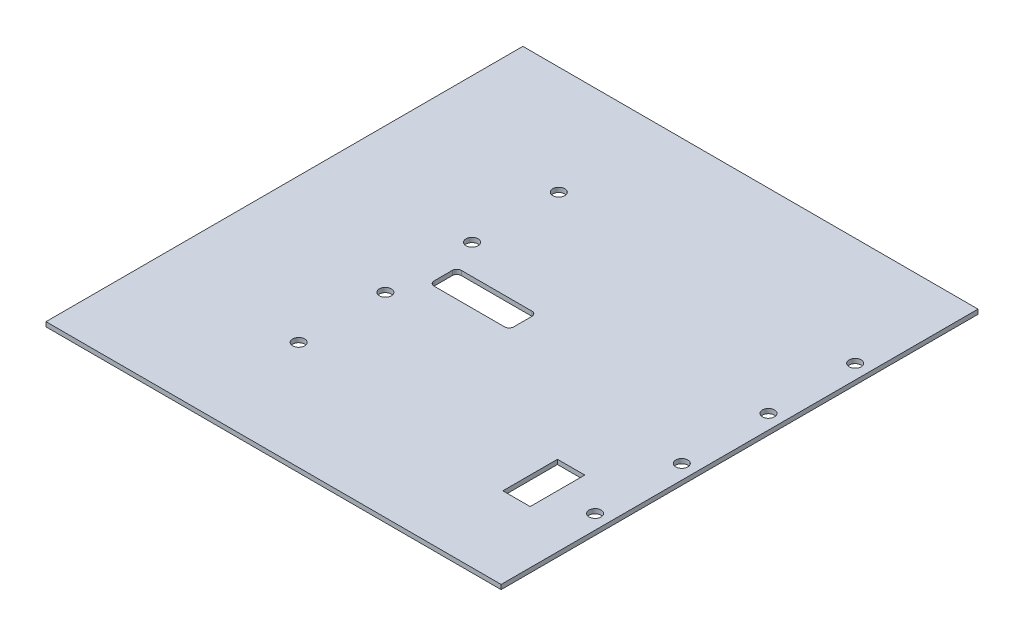
SolidWorks part; units mm, degrees
material "Thornel Mat VMA"
ref_plane "Front Plane" through (0, 0, 0) normal (0, 0, 1) x (1, 0, 0)
ref_plane "Top Plane" through (0, 0, 0) normal (0, 1, 0) x (1, 0, 0)
ref_plane "Right Plane" through (0, 0, 0) normal (1, 0, 0) x (0, 0, -1)
sketch "Sketch1" plane through (0, 0, 0) normal (0, 1, 0) x (1, 0, 0)
  line L1 (-100, -104.775) -> (100, -104.775)
  line L2 (-100, -104.775) -> (-100, 104.775)
  line L3 (-100, 104.775) -> (100, 104.775)
  line L4 (100, -104.775) -> (100, 104.775)
  line L5 (-100, -104.775) -> (100, 104.775) construction
  line L6 (-100, 104.775) -> (100, -104.775) construction
  point P0 (0, 0)
  dimension "D1" = 200
  dimension "D2" = 209.55
extrude "Boss-Extrude1" add sketch "Sketch1" along normal mid plane 2
sketch "Sketch2" plane through (0, 1, 0) normal (0, 1, 0) x (1, 0, 0)
  line L0 (-100, -104.775) -> (100, -104.775) construction
  line L1 (100, 104.775) -> (87.3, 104.775) construction
  line L2 (100, 104.775) -> (100, -104.775) construction
  line L3 (100, -104.775) -> (87.3, -104.775) construction
  line L4 (87.3, 104.775) -> (87.3, -104.775) construction
  line L5 (100, 104.775) -> (-100, 104.775) construction
  line L6 (-30.25, 104.775) -> (-42.95, 104.775) construction
  line L7 (-30.25, 104.775) -> (-30.25, -104.775) construction
  line L8 (-30.25, -104.775) -> (-42.95, -104.775) construction
  line L9 (-42.95, 104.775) -> (-42.95, -104.775) construction
  line L10 (93.65, 104.775) -> (93.65, -104.775) construction
  line L11 (-36.6, 104.775) -> (-36.6, -104.775) construction
  point P17 (93.65, 57.15)
  point P18 (-36.6, 57.15)
  point P20 (93.65, 19.05)
  point P21 (-36.6, 19.05)
  point P22 (93.65, -19.05)
  point P23 (-36.6, -19.05)
  point P24 (93.65, -57.15)
  point P25 (-36.6, -57.15)
  dimension "D1" = 12.7
  dimension "D2" = 12.7
  dimension "D3" = 130.25
  dimension "D4" = 47.625
  dimension "D6" = 38.1
  dimension "D5" = 4
hole_wizard "M5 Clearance Hole1" positions "Sketch3" profile "Sketch4" hole size "M5" standard "ANSI Metric" end condition up to next
sketch "Sketch3" plane through (0, 1, 0) normal (0, 1, 0) x (1, 0, 0)
  point P0 (-36.6, 57.15)
  point P3 (-36.6, 19.05)
  point P6 (-36.6, -19.05)
  point P9 (-36.6, -57.15)
  point P12 (93.65, -57.15)
  point P15 (93.65, -19.05)
  point P18 (93.65, 19.05)
  point P21 (93.65, 57.15)
sketch "Sketch4" plane through (-36.6, 1, -57.15) normal (1, 0, 0) x (0, 0, 1)
  line L0 (0, 0) -> (0, 2)
  line L1 (0, 2) -> (2.65, 2)
  line L2 (2.65, 2) -> (2.65, 0)
  line L5 (2.65, 0) -> (0, 0)
  line L11 (0, -6.35) -> (0, 107.95) construction
  dimension "Thru Hole Dia." = 5.3
  dimension "Thru Hole Depth" = 2
sketch "Sketch5" plane through (0, 1, 0) normal (0, 1, 0) x (1, 0, 0)
  line L0 (-30.25, 104.775) -> (-30.25, -104.775) construction
  line L1 (100, 104.775) -> (-100, 104.775) construction
  line L2 (-100, -104.775) -> (100, -104.775) construction
  line L3 (0, 0) -> (100, 0) construction
  line L4 (4.75, -6) -> (-30.25, -6)
  line L5 (4.75, -6) -> (4.75, 6)
  line L6 (4.75, 6) -> (-30.25, 6)
  line L7 (-30.25, -6) -> (-30.25, 6)
  line L8 (4.75, -6) -> (-30.25, 6) construction
  line L9 (4.75, 6) -> (-30.25, -6) construction
  line L10 (100, -104.775) -> (100, 104.775) construction
  circle A2 centre (-36.6, 19.05) radius 2.65 construction
  point P12 (-12.75, 0)
  dimension "D4" = 6.35
  dimension "D5" = 12
  dimension "D6" = 35
extrude "Cut-Extrude1" cut sketch "Sketch5" against normal through all
fillet "Fillet1" radius 2 4 edges at (4.75, 0, 6) (-30.25, 0, 6) (4.75, 0, -6) (-30.25, 0, -6)
sketch "Sketch8" plane through (0, 1, 0) normal (0, 1, 0) x (1, 0, 0)
  line L0 (100, -104.775) -> (100, 104.775) construction
  line L1 (64.75, -68.775) -> (76.75, -68.775)
  line L2 (64.75, -68.775) -> (64.75, -44.775)
  line L3 (64.75, -44.775) -> (76.75, -44.775)
  line L4 (76.75, -68.775) -> (76.75, -44.775)
  line L5 (64.75, -68.775) -> (76.75, -44.775) construction
  line L6 (64.75, -44.775) -> (76.75, -68.775) construction
  line L7 (-100, -104.775) -> (100, -104.775) construction
  point P0 (70.75, -56.775)
  dimension "D1" = 12
  dimension "D2" = 24
  dimension "D3" = 23.25
  dimension "D4" = 36
extrude "Cut-Extrude2" cut sketch "Sketch8" against normal through all
equation "\"D2@Sketch1\"=8.25in"
equation "\"D1@Sketch2\"=0.5in"
equation "\"D2@Sketch2\"=0.5in"
equation "\"D4@Sketch2\"=1.5in + 0.75in/2"
equation "\"D4@Sketch5\"=0.25in"
